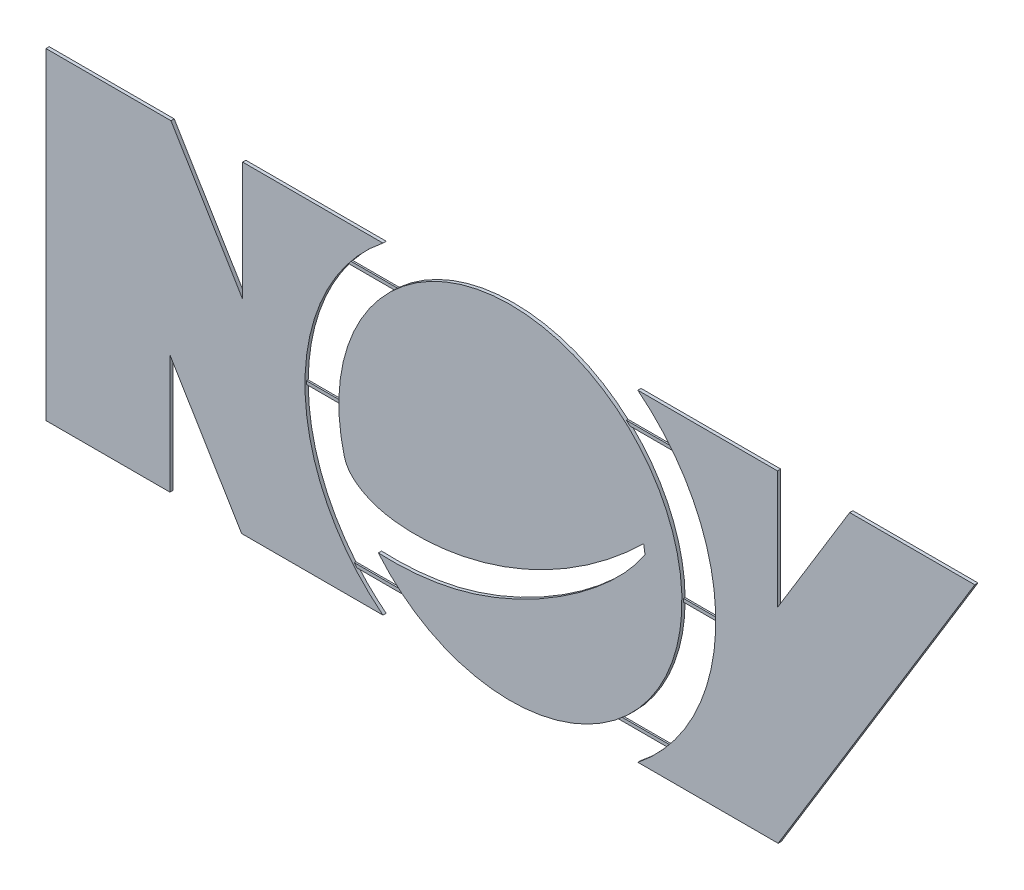
SolidWorks part; units mm, degrees
ref_plane "Front Plane" through (0, 0, 0) normal (0, 0, 1) x (1, 0, 0)
ref_plane "Top Plane" through (0, 0, 0) normal (0, 1, 0) x (1, 0, 0)
ref_plane "Right Plane" through (0, 0, 0) normal (1, 0, 0) x (0, 0, -1)
sketch "Sketch1" plane through (0, 0, 0) normal (0, 0, 1) x (1, 0, 0)
  line L0 (86.6339, 0.0014) -> (86.6339, 64.0014) construction
  line L1 (0, 62.0613) -> (23.3158, 62.0613)
  line L2 (23.3158, 62.0613) -> (36.6891, 39.8873)
  line L3 (36.6891, 39.8873) -> (36.6891, 62.0613)
  line L4 (36.6891, 62.0613) -> (62.8655, 62.0613)
  line L5 (0, 62.0613) -> (0, 1.95)
  line L6 (0, 1.95) -> (23.1112, 1.95)
  line L7 (23.1112, 1.95) -> (23.1112, 24.1454)
  line L8 (23.1112, 24.1454) -> (36.4974, 1.95)
  line L9 (36.4974, 1.95) -> (62.8567, 1.95)
  line L10 (110.412, 1.95) -> (136.5869, 1.95)
  line L11 (136.5869, 1.95) -> (173.2687, 62.0613)
  line L12 (173.2687, 62.0613) -> (149.9284, 62.0613)
  line L13 (149.9284, 62.0613) -> (136.4682, 40.0038)
  line L14 (136.4682, 40.0038) -> (136.4682, 62.0613)
  line L15 (136.4682, 62.0613) -> (110.4031, 62.0613)
  line L16 (0, 64.0043) -> (173.2687, 0) construction
  line L17 (173.2687, 64.0043) -> (0, 64.0043) construction
  line L18 (173.2687, 64.0043) -> (173.2687, 0) construction
  line L19 (173.2687, 0) -> (0, 0) construction
  line L20 (0, 64.0043) -> (0, 0) construction
  line L21 (111.4906, 37.8163) -> (111.7516, 36.1382)
  arc A0 (62.8655, 62.0613) -> (62.8567, 1.95) centre (86.6343, 32.0021) ccw
  arc A1 (110.412, 1.95) -> (110.4031, 62.0613) centre (86.6343, 32.0021) ccw
  arc A2 (61.9998, 11.5748) -> (55.6658, 23.9345) centre (86.6343, 32.0021) ccw
  spline S0 degree 3 poles (61.9998, 11.5748) (65.6518, 11.3847) (84.023, 12.1718) (105.2441, 26.2465) (111.7516, 36.1382) knots 0 0 0 0 0.285158 1 1 1 1
  spline S1 degree 3 poles (55.6207, 24.1096) (56.1961, 21.7048) (60.2552, 18.8924) (68.0001, 17.6879) (77.626, 18.4752) (88.0507, 21.7096) (99.9709, 27.9012) (107.3037, 33.692) (111.4906, 37.8163) knots 0 0 0 0 0.111444 0.211567 0.368518 0.562067 0.722926 1 1 1 1
  dimension "D1" = 64
  dimension "D2" = 1.95
extrude "Boss-Extrude1" add sketch "Sketch1" along normal blind 0.6 contours A0 L4 L3 L2 L1 L5 L6 L7 L8 L9 | A2 S1 L21 S0 | A1 L10 L11 L12 L13 L14 L15 region at (26.177, 32.0083, 0) region at (138.973, 36.0079, 0) region at (87.1161, 33.1474, 0)
ref_plane "Plane1" through (86.635, 0, 0) normal (-1, 0, 0) x (0, 0, 1)
ref_plane "Plane2" through (0, 32.0056, 0) normal (0, 1, 0) x (1, 0, 0)
sketch "Sketch2" plane through (0, 0, 0) normal (0, 0, 1) x (1, 0, 0)
  line L0 (56.6338, 55.8449) -> (65.2882, 55.8449)
  line L1 (56.1666, 55.2449) -> (64.6364, 55.2449)
  line L2 (110.412, 1.95) -> (136.5869, 1.95) construction
  line L3 (136.5869, 1.95) -> (173.2687, 62.0613) construction
  line L4 (173.2687, 62.0613) -> (149.9284, 62.0613) construction
  line L5 (149.9284, 62.0613) -> (136.4682, 40.0038) construction
  line L6 (136.4682, 40.0038) -> (136.4682, 62.0613) construction
  line L7 (136.4682, 62.0613) -> (110.4031, 62.0613) construction
  line L8 (62.8655, 62.0613) -> (36.6891, 62.0613) construction
  line L9 (36.6891, 62.0613) -> (36.6891, 39.8873) construction
  line L10 (36.6891, 39.8873) -> (23.3158, 62.0613) construction
  line L11 (23.3158, 62.0613) -> (0, 62.0613) construction
  line L12 (0, 62.0613) -> (0, 1.95) construction
  line L13 (0, 1.95) -> (23.1112, 1.95) construction
  line L14 (23.1112, 1.95) -> (23.1112, 24.1454) construction
  line L15 (23.1112, 24.1454) -> (36.4974, 1.95) construction
  line L16 (36.4974, 1.95) -> (62.8567, 1.95) construction
  line L17 (111.4906, 37.8163) -> (111.7516, 36.1382) construction
  line L18 (110.412, 1.95) -> (136.5869, 1.95)
  line L19 (136.5869, 1.95) -> (173.2687, 62.0613)
  line L20 (173.2687, 62.0613) -> (149.9284, 62.0613)
  line L21 (149.9284, 62.0613) -> (136.4682, 40.0038)
  line L22 (136.4682, 40.0038) -> (136.4682, 62.0613)
  line L23 (136.4682, 62.0613) -> (110.4031, 62.0613)
  line L24 (62.8655, 62.0613) -> (36.6891, 62.0613)
  line L25 (36.6891, 62.0613) -> (36.6891, 39.8873)
  line L26 (36.6891, 39.8873) -> (23.3158, 62.0613)
  line L27 (23.3158, 62.0613) -> (0, 62.0613)
  line L28 (0, 62.0613) -> (0, 1.95)
  line L29 (0, 1.95) -> (23.1112, 1.95)
  line L30 (23.1112, 1.95) -> (23.1112, 24.1454)
  line L31 (23.1112, 24.1454) -> (36.4974, 1.95)
  line L32 (36.4974, 1.95) -> (62.8567, 1.95)
  line L33 (111.4906, 37.8163) -> (111.7516, 36.1382)
  line L34 (48.3151, 32.3863) -> (54.6345, 32.3863)
  line L35 (48.3138, 31.7863) -> (54.6329, 31.7863)
  line L36 (57.2015, 7.4621) -> (66.0936, 7.4621)
  line L37 (57.7123, 6.8621) -> (66.8325, 6.8621)
  line L38 (116.0672, 7.4621) -> (107.1751, 7.4621)
  line L39 (115.5564, 6.8621) -> (106.4362, 6.8621)
  line L40 (124.9535, 32.3863) -> (118.6342, 32.3863)
  line L41 (124.9549, 31.7863) -> (118.6357, 31.7863)
  line L42 (117.1021, 55.2449) -> (108.6323, 55.2449)
  line L43 (116.6348, 55.8449) -> (107.9805, 55.8449)
  arc A0 (62.8655, 62.0613) -> (62.8567, 1.95) centre (86.6343, 32.0021) ccw construction
  arc A1 (61.9998, 11.5748) -> (55.6658, 23.9345) centre (86.6343, 32.0021) ccw construction
  arc A2 (110.412, 1.95) -> (110.4031, 62.0613) centre (86.6343, 32.0021) ccw construction
  arc A3 (62.8655, 62.0613) -> (62.8567, 1.95) centre (86.6343, 32.0021) ccw construction
  arc A4 (110.412, 1.95) -> (110.4031, 62.0613) centre (86.6343, 32.0021) ccw
  arc A5 (62.8655, 62.0613) -> (62.8567, 1.95) centre (86.6343, 32.0021) ccw
  arc A6 (61.9998, 11.5748) -> (55.6658, 23.9345) centre (86.6343, 32.0021) ccw
  spline S0 degree 3 poles (1936.382, 700.1061) (24.2852, 109.4543) (36.9497, 22.5168) (68.0001, 17.6879) (77.626, 18.4752) (88.0507, 21.7096) (229.6471, 95.259) (107.5698, 583.7012) (-1609.4835, -920.0756) knots -1.10892 -1.10892 -1.10892 -1.10892 0.111444 0.211567 0.368518 0.562067 0.722926 7.869722 7.869722 7.869722 7.869722 only from (55.6658, 23.9345) to (111.4906, 37.8163) construction
  spline S1 degree 3 poles (-1737.8727, -714.4512) (294.8147, 299.4838) (57.091, -167.8769) (-18.0464, 122.8026) (1968.3755, -590.4602) knots -3.597505 -3.597505 -3.597505 -3.597505 0.714842 3.955537 3.955537 3.955537 3.955537 only from (111.7516, 36.1382) to (61.9998, 11.5748) construction
  spline S2 degree 3 poles (55.6658, 23.9345) (56.301, 21.6325) (60.3126, 18.8835) (68.0001, 17.6879) (77.626, 18.4752) (88.0507, 21.7096) (99.9709, 27.9012) (107.3037, 33.692) (111.4906, 37.8163) knots 0.002731 0.002731 0.002731 0.002731 0.111444 0.211567 0.368518 0.562067 0.722926 1 1 1 1
  spline S3 degree 3 poles (111.7516, 36.1382) (105.2441, 26.2465) (84.023, 12.1718) (65.6518, 11.3847) (61.9998, 11.5748) knots 0 0 0 0 0.714842 1 1 1 1
  dimension "D1" = 0.6
  dimension "D2" = 0.6
  dimension "D3" = 0.6
  dimension "D4" = 0.6
  dimension "D5" = 0.6
  dimension "D6" = 0.6
extrude "Boss-Extrude2" add sketch "Sketch2" along normal blind 0.3 contours A6 L0 A5 L1 | A6 L36 A5 L37 | A6 L34 A5 L35 | A6 L39 A4 L38 | A6 L41 A4 L40 | A6 L42 A4 L43 region at (60.68, 55.546, 0) region at (112.5887, 55.546, 0) region at (51.4732, 32.0863, 0) region at (121.7954, 32.0863, 0) region at (61.9585, 7.1608, 0) region at (111.3101, 7.1608, 0)
